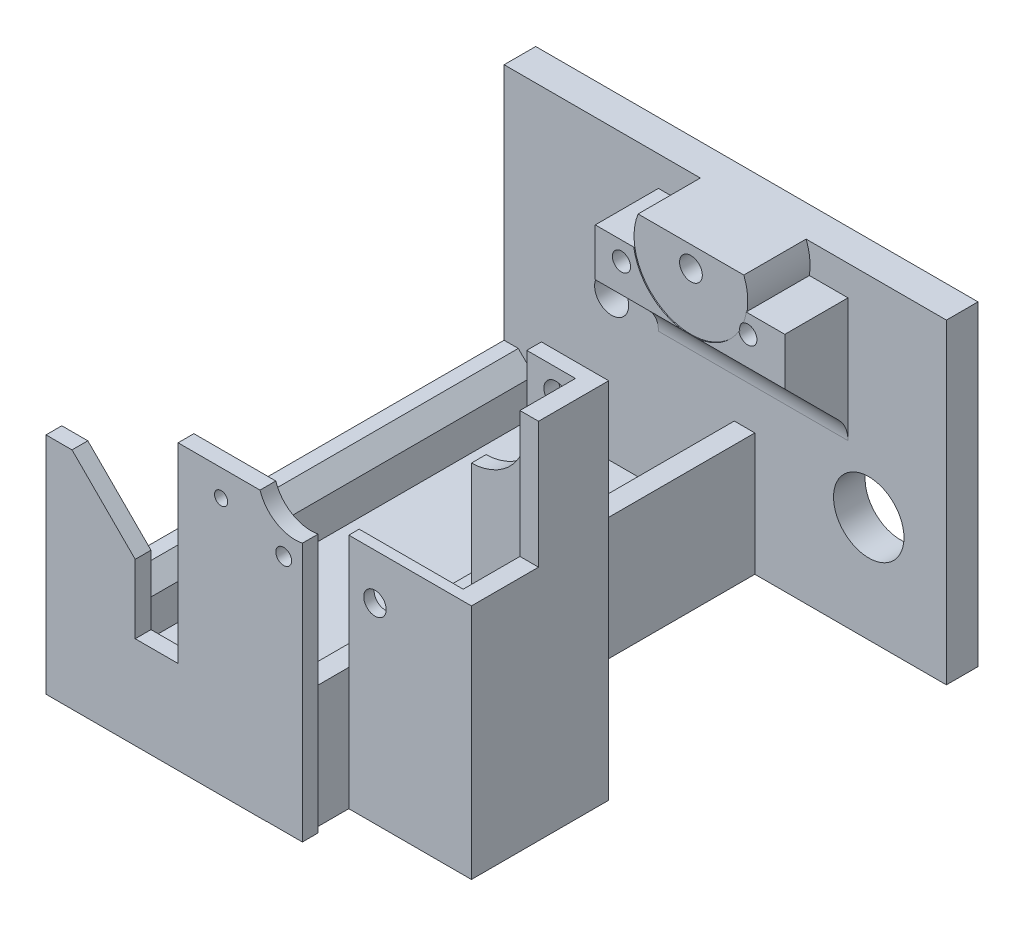
SolidWorks part; units mm, degrees
material "ABS"
ref_plane "Front Plane" through (0, 0, 0) normal (0, 0, 1) x (1, 0, 0)
ref_plane "Top Plane" through (0, 0, 0) normal (0, 1, 0) x (1, 0, 0)
ref_plane "Right Plane" through (0, 0, 0) normal (1, 0, 0) x (0, 0, -1)
sketch "Sketch1" plane through (0, 0, 0) normal (0, 0, 1) x (1, 0, 0)
  line L1 (-65.5446, 32.6733) -> (74.4554, 32.6733)
  line L2 (-65.5446, 32.6733) -> (-65.5446, -67.3267)
  line L3 (-65.5446, -67.3267) -> (74.4554, -67.3267)
  line L4 (74.4554, 32.6733) -> (74.4554, -67.3267)
  dimension "D1" = 100
  dimension "D2" = 140
extrude "Boss-Extrude1" add sketch "Sketch1" along normal blind 10
sketch "Sketch2" plane through (0, 0, 10) normal (0, 0, 1) x (1, 0, 0)
  line L0 (-65.5446, -67.3267) -> (-65.5446, -42.849)
  line L3 (-65.5446, -67.3267) -> (7.3151, -67.3267)
  line L5 (-65.5446, -67.3267) -> (74.4554, -67.3267) construction
  line L8 (-65.5446, 32.6733) -> (-65.5446, -67.3267) construction
  line L9 (-65.5446, -42.849) -> (-56.0483, -42.849)
  line L10 (-56.0483, -42.849) -> (-56.0483, -59.0904)
  line L11 (-56.0483, -59.0904) -> (7.3151, -59.0904)
  line L12 (7.3151, -59.0904) -> (7.3151, -28.5708)
  line L13 (7.3151, -28.5708) -> (13.8255, -28.5708)
  line L14 (13.8255, -28.5708) -> (13.8255, -67.3267)
  line L15 (13.8255, -67.3267) -> (7.3151, -67.3267)
extrude "Boss-Extrude2" add sketch "Sketch2" along normal blind 140
sketch "Sketch3" plane through (0, 0, 10) normal (0, 0, 1) x (1, 0, 0)
  line L1 (-16.6941, 23.1955) -> (43.3059, 23.1955)
  line L2 (-16.6941, 23.1955) -> (-16.6941, 8.1955)
  line L3 (-16.6941, 8.1955) -> (43.3059, 8.1955)
  line L4 (43.3059, 23.1955) -> (43.3059, 8.1955)
  dimension "D1" = 15
  dimension "D2" = 60
extrude "Boss-Extrude3" add sketch "Sketch3" along normal blind 20
sketch "Sketch4" plane through (0, 0, 10) normal (0, 0, 1) x (1, 0, 0)
  line L0 (43.3059, 8.1955) -> (43.3059, 23.1955) construction
  circle A0 centre (13.3059, 26.0432) radius 18
  dimension "D1" = 36
  dimension "D2" = 30
extrude "Boss-Extrude4" add sketch "Sketch4" along normal blind 20
sketch "Sketch6" plane through (0, 0, 30) normal (0, 0, 1) x (1, 0, 0)
  circle A0 centre (13.3059, 26.0432) radius 3.5973
  arc A1 (31.0792, 23.1955) -> (-4.4674, 23.1955) centre (13.3059, 26.0432) ccw construction
extrude "Cut-Extrude2" cut sketch "Sketch6" against normal blind 100
sketch "Sketch5" plane through (0, 0, 30) normal (0, 0, 1) x (1, 0, 0)
  line L0 (74.4554, 32.6733) -> (30.0404, 32.6733) construction
  line L1 (-13.303, 47.4) -> (34.4273, 47.4)
  line L2 (-13.303, 47.4) -> (-13.303, 32.6733)
  line L3 (-13.303, 32.6733) -> (34.4273, 32.6733)
  line L4 (34.4273, 47.4) -> (34.4273, 32.6733)
extrude "Cut-Extrude1" cut sketch "Sketch5" against normal blind 20
sketch "Sketch7" plane through (0, 0, 30) normal (0, 0, 1) x (1, 0, 0)
  circle A0 centre (-8.3949, 17.2978) radius 2.8779
extrude "Cut-Extrude3" cut sketch "Sketch7" against normal blind 100
pattern_linear "LPattern1" count 2 spacing 40 along (1, 0, 0) of "Cut-Extrude3"
sketch "Sketch9" plane through (0, 0, 150) normal (0, 0, 1) x (1, 0, 0)
  line L0 (-65.5446, 32.6733) -> (-65.5446, -42.849) construction
  line L1 (4.1877, 3.7072) -> (-65.5446, 3.7072)
  line L2 (4.1877, 3.7072) -> (4.1877, -67.3896)
  line L3 (4.1877, -67.3896) -> (-65.5446, -67.3896)
  line L4 (-65.5446, 3.7072) -> (-65.5446, -67.3896)
extrude "Boss-Extrude5" add sketch "Sketch9" along normal blind 5
chamfer "Chamfer1" distance 20 angle 45 2 edges at (29.4741, 8.1955, 10) (-2.8623, 8.1955, 10)
sketch "Sketch10" plane through (0, 0, 155) normal (0, 0, 1) x (1, 0, 0)
  line L1 (-37.3082, 6.7363) -> (-23.6547, 6.7363)
  line L2 (-37.3082, 6.7363) -> (-37.3082, -38.0615)
  line L3 (-37.3082, -38.0615) -> (-23.6547, -38.0615)
  line L4 (-23.6547, 6.7363) -> (-23.6547, -38.0615)
extrude "Cut-Extrude4" cut sketch "Sketch10" against normal blind 10
sketch "Sketch11" plane through (0, 0, 155) normal (0, 0, 1) x (1, 0, 0)
  line L0 (13.8255, -67.3267) -> (74.4554, -67.3267) construction
  line L1 (-23.7439, 22.4423) -> (15.6103, 22.4423)
  line L2 (-23.7439, 22.4423) -> (-23.7439, -67.3267)
  line L3 (-23.7439, -67.3267) -> (15.6103, -67.3267)
  line L4 (15.6103, 22.4423) -> (15.6103, -67.3267)
extrude "Boss-Extrude6" add sketch "Sketch11" against normal blind 5
sketch "Sketch12" plane through (0, 0, 155) normal (0, 0, 1) x (1, 0, 0)
  circle A0 centre (13.3059, 26.0432) radius 11.6785
extrude "Cut-Extrude5" cut sketch "Sketch12" against normal blind 10
sketch "Sketch13" plane through (0, 0, 155) normal (0, 0, 1) x (1, 0, 0)
  circle A0 centre (-10.1053, 14.0773) radius 2.089
  circle A1 centre (9.687, 8.0077) radius 2.4987
extrude "Cut-Extrude6" cut sketch "Sketch13" against normal blind 10
fillet "Fillet2" radius 10 1 edges at (13.3059, -11.8045, 10)
chamfer "Chamfer2" distance 5 angle 45 1 edges at (-56.0483, -42.849, 80)
sketch "Sketch14" plane through (0, 0, 10) normal (0, 0, 1) x (1, 0, 0)
  circle A0 centre (-31.5077, -13.6101) radius 5.3914
  circle A1 centre (49.8779, -33.6888) radius 11.1548
extrude "Cut-Extrude7" cut sketch "Sketch14" against normal blind 10
chamfer "Chamfer3" distance 20 angle 45 1 edges at (-37.3082, 3.7072, 152.5)
sketch "Sketch15" plane through (0, -67.3267, 0) normal (0, -1, 0) x (1, 0, 0)
  line L1 (4.5956, 95.0738) -> (52.6384, 95.0738)
  line L2 (4.5956, 95.0738) -> (4.5956, 138.5253)
  line L3 (4.5956, 138.5253) -> (52.6384, 138.5253)
  line L4 (52.6384, 95.0738) -> (52.6384, 138.5253)
extrude "Boss-Extrude7" add sketch "Sketch15" against normal blind 5
sketch "Sketch16" plane through (0, -62.3267, 0) normal (0, 1, 0) x (1, 0, 0)
  line L8 (13.8255, -135.2423) -> (13.8255, -138.5253)
  line L9 (13.8255, -138.5253) -> (13.8255, -95.0738) construction
  line L10 (13.8255, -138.5253) -> (52.6384, -138.5253)
  line L11 (52.6384, -138.5253) -> (52.6384, -116.7995)
  line L12 (52.6384, -95.0738) -> (52.6384, -138.5253) construction
  line L13 (52.6384, -116.7995) -> (46.7483, -116.7995)
  line L14 (46.7483, -116.7995) -> (46.7483, -135.2423)
  line L15 (46.7483, -135.2423) -> (13.8255, -135.2423)
extrude "Boss-Extrude8" add sketch "Sketch16" along normal blind 70
sketch "Sketch17" plane through (0, 7.6733, 0) normal (0, 1, 0) x (1, 0, 0)
  line L1 (28.8586, -179.0031) -> (38.4745, -179.0031)
  line L2 (28.8586, -179.0031) -> (28.8586, -197.9959)
  line L3 (28.8586, -197.9959) -> (38.4745, -197.9959)
  line L4 (38.4745, -179.0031) -> (38.4745, -197.9959)
extrude "Cut-Extrude8" cut sketch "Sketch17" against normal blind 20 rebuild error yes
sketch "Sketch18" plane through (0, 0, 138.5253) normal (0, 0, 1) x (1, 0, 0)
  circle A0 centre (22.1124, -6.8448) radius 3.5565
  point P2 (22.1124, -6.8448)
extrude "Cut-Extrude9" cut sketch "Sketch18" against normal blind 20
sketch "Sketch19" plane through (0, -62.3267, 0) normal (0, 1, 0) x (1, 0, 0)
  line L0 (13.8199, -95.0738) -> (13.8199, -99.7086)
  line L3 (13.8199, -99.7086) -> (46.7483, -99.7086)
  line L6 (46.7483, -99.7086) -> (46.7483, -117.2823)
  line L7 (46.7483, -117.2823) -> (52.6384, -117.2823)
  line L8 (52.6384, -95.0738) -> (52.6384, -116.7995) construction
  line L9 (52.6384, -117.2823) -> (52.6384, -95.0738)
  line L10 (52.6384, -95.0738) -> (13.8199, -95.0738)
  point P4 (0, 0)
extrude "Boss-Extrude9" add sketch "Sketch19" along normal blind 110
sketch "Sketch20" plane through (0, 0, 99.7086) normal (0, 0, 1) x (1, 0, 0)
  line L0 (13.3059, 26.0432) -> (13.3059, 51.1413) construction
  line L1 (-4.7235, 26.0432) -> (-4.7235, 51.1413)
  line L2 (31.3354, 26.0432) -> (31.3354, 51.1413)
  arc A0 (-4.7235, 26.0432) -> (31.3354, 26.0432) centre (13.3059, 26.0432) ccw
  arc A1 (31.3354, 51.1413) -> (-4.7235, 51.1413) centre (13.3059, 51.1413) ccw
  point P3 (13.3059, 38.5923)
extrude "Cut-Extrude10" cut sketch "Sketch20" against normal blind 70
sketch "Sketch21" plane through (0, 0, 99.7086) normal (0, 0, 1) x (1, 0, 0)
  circle A0 centre (40.582, 40.031) radius 3.8105
extrude "Cut-Extrude11" cut sketch "Sketch21" against normal blind 70
